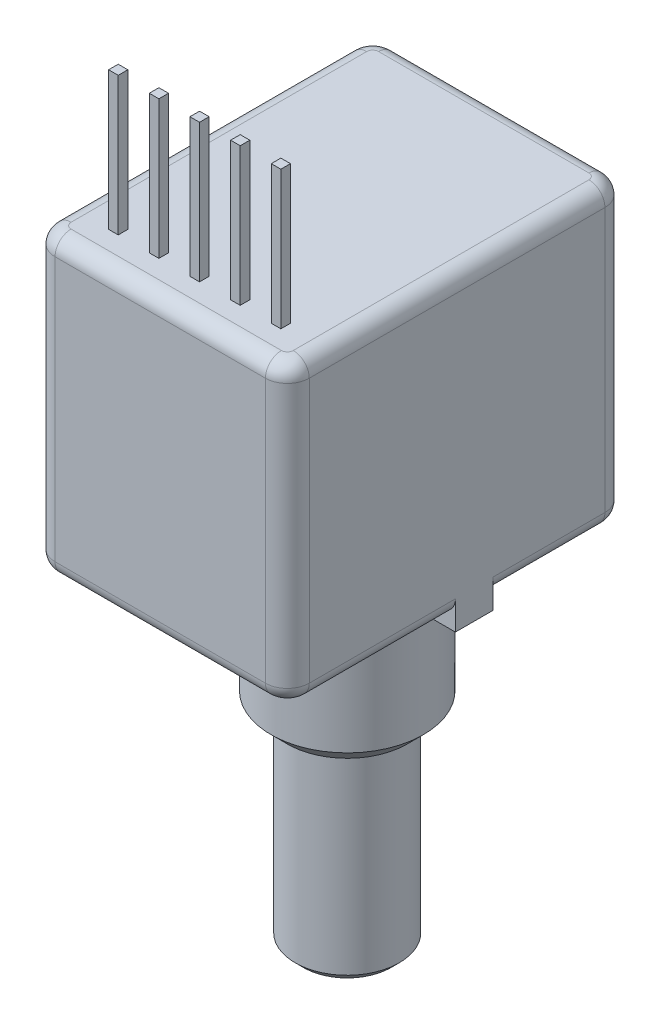
SolidWorks part; units mm, degrees
ref_plane "Спереди" through (0, 0, 0) normal (0, 0, 1) x (1, 0, 0)
ref_plane "Сверху" through (0, 0, 0) normal (0, 1, 0) x (1, 0, 0)
ref_plane "Справа" through (0, 0, 0) normal (1, 0, 0) x (0, 0, -1)
sketch "Эскиз2" plane through (0, 0, 0) normal (0, 1, 0) x (1, 0, 0)
  line L1 (0, 0) -> (15.88, 0)
  line L2 (0, 0) -> (0, 21.21)
  line L3 (0, 21.21) -> (15.88, 21.21)
  line L4 (15.88, 0) -> (15.88, 21.21)
  dimension "D1" = 21.21
  dimension "D2" = 15.88
extrude "Бобышка-Вытянуть1" add sketch "Эскиз2" along normal blind 18.5
fillet "Скругление1" radius 1.37 4 edges at (0, 9.25, -21.21) (15.88, 9.25, -21.21) (15.88, 9.25, 0) (0, 9.25, 0)
fillet "Скругление2" radius 1 16 edges at (15.4787, 18.5, -20.8087) (15.88, 18.5, -10.605) (15.4787, 18.5, -0.4013) (7.94, 18.5, 0) (0.4013, 18.5, -0.4013) (0, 18.5, -10.605) (0.4013, 18.5, -20.8087) (15.4787, 0, -20.8087) (15.88, 0, -10.605) (15.4787, 0, -0.4013) (7.94, 0, 0) (0.4013, 0, -0.4013) (0, 0, -10.605) (0.4013, 0, -20.8087) (7.94, 18.5, -21.21) (7.94, 0, -21.21)
sketch "Эскиз3" plane through (0, 0, 0) normal (0, -1, 0) x (1, 0, 0)
  line L0 (7.94, -21.21) -> (7.94, -11.68) construction
  line L1 (14.51, -21.21) -> (1.37, -21.21) construction
  circle A0 centre (7.94, -11.68) radius 4.7625
  dimension "D2" = 9.525
  dimension "D1" = 9.53
extrude "Бобышка-Вытянуть2" add sketch "Эскиз3" along normal blind 9.53
cosmetic thread "Условное изображение резьбы2" parameters "D2"=8.2652
sketch "Эскиз4" plane through (0, -9.53, 0) normal (0, -1, 0) x (1, 0, 0)
  circle A0 centre (7.94, -11.68) radius 3.25
  dimension "D1" = 6.5
extrude "Бобышка-Вытянуть3" add sketch "Эскиз4" along normal blind 12.6
chamfer "Фаска1" distance 0.5 angle 45 1 edges at (7.94, -22.13, -14.93)
chamfer "Фаска2" distance 1 angle 45 1 edges at (7.94, -9.53, -16.4425)
sketch "Эскиз5" plane through (0, 0, 0) normal (0, -1, 0) x (1, 0, 0)
  circle A0 centre (7.94, -11.68) radius 5.2
  dimension "D1" = 10.4
extrude "Бобышка-Вытянуть4" add sketch "Эскиз5" along normal blind 1.57
sketch "Эскиз6" plane through (0, 0, 0) normal (0, -1, 0) x (1, 0, 0)
  line L0 (7.94, -11.68) -> (15.88, -11.68) construction
  line L1 (15.88, -1.37) -> (15.88, -19.84) construction
  line L3 (14.51, -10.5) -> (15.88, -10.5)
  line L4 (14.51, -10.5) -> (14.51, -12.86)
  line L5 (14.51, -12.86) -> (15.88, -12.86)
  line L6 (15.88, -10.5) -> (15.88, -12.86)
  point P9 (15.88, -11.68)
  dimension "D1" = 2.36
  dimension "D2" = 1.37
extrude "Бобышка-Вытянуть5" add sketch "Эскиз6" along normal blind 0.8
extrude "Бобышка-Вытянуть6" add sketch "Эскиз6<3>" against normal blind 2
sketch "Эскиз6<3>" plane through (0, 0, 0) normal (0, -1, 0) x (1, 0, 0) same geometry as "Эскиз6"
sketch "Эскиз7" plane through (0, 18.5, 0) normal (0, 1, 0) x (1, 0, 0)
  line L0 (7.94, 11.68) -> (7.94, 2.155) construction
  line L5 (10.78, 2.755) -> (10.18, 2.755)
  line L6 (10.18, 2.755) -> (10.18, 2.155)
  line L7 (10.78, 2.155) -> (10.18, 2.155)
  line L8 (10.78, 2.755) -> (10.78, 2.155)
  line L9 (13.32, 2.755) -> (12.72, 2.755)
  line L10 (12.72, 2.755) -> (12.72, 2.155)
  line L11 (13.32, 2.155) -> (12.72, 2.155)
  line L12 (13.32, 2.755) -> (13.32, 2.155)
  line L17 (10.78, 2.755) -> (10.18, 2.755)
  line L18 (10.18, 2.755) -> (10.18, 2.155)
  line L19 (10.78, 2.155) -> (10.18, 2.155)
  line L20 (10.78, 2.755) -> (10.78, 2.155)
  line L21 (5.7, 2.755) -> (5.1, 2.755)
  line L22 (5.1, 2.755) -> (5.1, 2.155)
  line L23 (5.7, 2.155) -> (5.1, 2.155)
  line L24 (5.7, 2.755) -> (5.7, 2.155)
  line L25 (8.24, 2.755) -> (7.64, 2.755)
  line L26 (7.64, 2.755) -> (7.64, 2.155)
  line L27 (8.24, 2.155) -> (7.64, 2.155)
  line L28 (8.24, 2.755) -> (8.24, 2.155)
  line L29 (5.7, 2.755) -> (5.1, 2.755)
  line L30 (5.1, 2.755) -> (5.1, 2.155)
  line L31 (5.7, 2.155) -> (5.1, 2.155)
  line L32 (5.7, 2.755) -> (5.7, 2.155)
  line L33 (3.16, 2.755) -> (2.56, 2.755)
  line L34 (2.56, 2.755) -> (2.56, 2.155)
  line L35 (3.16, 2.155) -> (2.56, 2.155)
  line L36 (3.16, 2.755) -> (3.16, 2.155)
  point P0 (7.94, 2.155)
  point P1 (0, 0)
  point P2 (0, 0)
  point P7 (7.94, 2.155)
  dimension "D1" = 0.6
  dimension "D2" = 9.525
  dimension "D3" = 2.54
  dimension "D4" = 2.54
  dimension "D5" = 2.54
  dimension "D6" = 2.54
extrude "Бобышка-Вытянуть7" add sketch "Эскиз7" along normal blind 8.636 contours L36 L33 L34 L35 | L24 L21 L22 L23 | L25 L0 L27 L28 | L8 L5 L6 L7 | L12 L9 L10 L11 | L0 L25 L26 L27 region at (8.09, 18.5, -2.455) region at (7.79, 18.5, -2.455) region at (10.48, 18.5, -2.455) region at (13.02, 18.5, -2.455) region at (5.4, 18.5, -2.455) region at (2.86, 18.5, -2.455)
